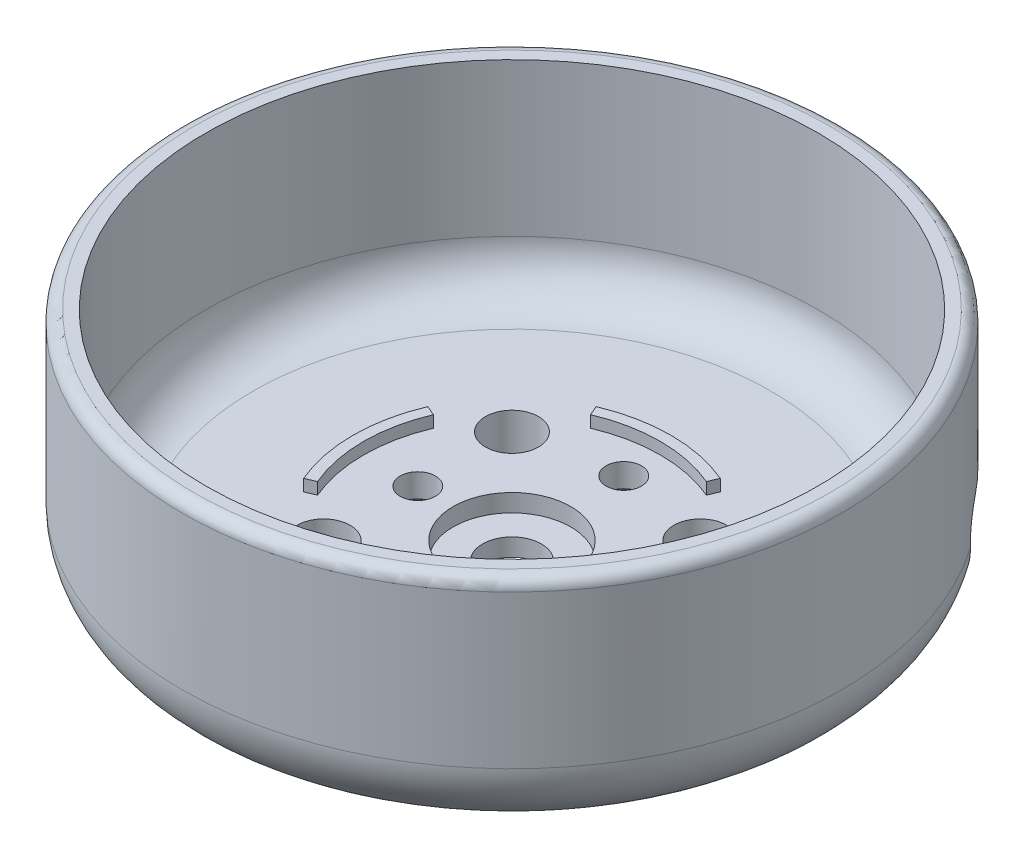
SolidWorks part; units mm, degrees
ref_plane "Front Plane" through (0, 0, 0) normal (0, 0, 1) x (1, 0, 0)
ref_plane "Top Plane" through (0, 0, 0) normal (0, 1, 0) x (1, 0, 0)
ref_plane "Right Plane" through (0, 0, 0) normal (1, 0, 0) x (0, 0, -1)
sketch "Sketch1" plane through (0, 0, 0) normal (0, 1, 0) x (1, 0, 0)
  circle A0 centre (0, 0) radius 9.5 construction
  circle A1 centre (0, 0) radius 8 construction
  circle A2 centre (0, 9.5) radius 1.5
  circle A3 centre (0, -9.5) radius 1.5
  circle A4 centre (-8, 0) radius 1.5
  circle A5 centre (8, 0) radius 1.5
  circle A6 centre (0, 0) radius 2.5
  circle A7 centre (0, 0) radius 26
  dimension "D1" = 8
  dimension "D3" = 3
  dimension "D4" = 3
  dimension "D5" = 3
  dimension "D6" = 3
  dimension "D7" = 52
  dimension "D8" = 5
  dimension "D2" = 9.5
extrude "Boss-Extrude1" add sketch "Sketch1" along normal blind 3
chamfer "Chamfer2" distance 1 angle 45 4 edges at (-8, 0, 1.5) (0, 0, -8) (8, 0, 1.5) (0, 0, 11)
sketch "Sketch3" plane through (0, 0, 0) normal (0, -1, 0) x (1, 0, 0)
  circle A0 centre (0, 0) radius 26 construction
  circle A1 centre (0, 0) radius 26
  circle A2 centre (0, 0) radius 28
  dimension "D1" = 2
extrude "Boss-Extrude3" add sketch "Sketch3" against normal blind 20
fillet "Fillet3" radius 4 1 edges at (0, 3, 26)
fillet "Fillet4" radius 6 1 edges at (0, 0, -28)
sketch "Sketch4" plane through (0, 3, 0) normal (0, 1, 0) x (1, 0, 0)
  line L0 (-9.5459, 9.5459) -> (9.5459, -9.5459) construction
  line L1 (-9.5459, -9.5459) -> (9.5459, 9.5459) construction
  line L2 (0, 0) -> (0, 22) construction
  line L3 (0, 0) -> (-5.2749, 12.4268) construction
  line L4 (0, 0) -> (-12.4268, 5.2749) construction
  line L5 (-12.4268, 5.2749) -> (-11.5984, 4.9232)
  line L6 (-5.2749, 12.4268) -> (-4.9232, 11.5984)
  line L7 (12.4268, 5.2749) -> (11.5984, 4.9232)
  line L8 (5.2749, 12.4268) -> (4.9232, 11.5984)
  line L9 (5.2749, -12.4268) -> (4.9232, -11.5984)
  line L10 (12.4268, -5.2749) -> (11.5984, -4.9232)
  line L11 (-12.4268, -5.2749) -> (-11.5984, -4.9232)
  line L12 (-5.2749, -12.4268) -> (-4.9232, -11.5984)
  arc A0 (-11.5984, 4.9232) -> (-11.5984, -4.9232) centre (0, 0) ccw
  arc A1 (-12.4268, 5.2749) -> (-12.4268, -5.2749) centre (0, 0) ccw
  circle A2 centre (0, 0) radius 22 construction
  arc A3 (-4.9232, -11.5984) -> (4.9232, -11.5984) centre (0, 0) ccw
  arc A4 (-5.2749, -12.4268) -> (5.2749, -12.4268) centre (0, 0) ccw
  arc A5 (11.5984, -4.9232) -> (11.5984, 4.9232) centre (0, 0) ccw
  arc A6 (12.4268, -5.2749) -> (12.4268, 5.2749) centre (0, 0) ccw
  arc A7 (4.9232, 11.5984) -> (-4.9232, 11.5984) centre (0, 0) ccw
  arc A8 (5.2749, 12.4268) -> (-5.2749, 12.4268) centre (0, 0) ccw
  point P21 (0, 0)
  point P30 (0, 0)
  dimension "D1" = 25.2
  dimension "D2" = 27
  dimension "D3" = 45
  dimension "D4" = 45
  dimension "D5" = 22
  dimension "D6" = 22
  dimension "D7" = 4
extrude "Boss-Extrude4" add sketch "Sketch4" along normal blind 1
sketch "Sketch5" plane through (0, 0, 0) normal (0, -1, 0) x (1, 0, 0)
  line L1 (-8, -8) -> (8, -8) construction
  line L2 (-8, -8) -> (-8, 8) construction
  line L3 (-8, 8) -> (8, 8) construction
  line L4 (8, -8) -> (8, 8) construction
  line L5 (-8, -8) -> (8, 8) construction
  line L6 (-8, 8) -> (8, -8) construction
  circle A1 centre (-8, 8) radius 2.25
  circle A2 centre (8, 8) radius 2.25
  circle A3 centre (8, -8) radius 2.25
  circle A4 centre (-8, -8) radius 2.25
  circle A5 centre (-8, 8) radius 4
  circle A6 centre (8, 8) radius 4
  circle A7 centre (8, -8) radius 4
  circle A8 centre (-8, -8) radius 4
  point P0 (0, 0)
  dimension "D1" = 16
  dimension "D3" = 4.5
  dimension "D4" = 4.5
  dimension "D5" = 4.5
  dimension "D6" = 4.5
  dimension "D7" = 8
  dimension "D8" = 8
  dimension "D9" = 8
  dimension "D10" = 8
  dimension "D2" = 16
extrude "Boss-Extrude5" add sketch "Sketch5" along normal blind 2.8
sketch "Sketch7" plane through (0, 0, 0) normal (0, -1, 0) x (1, 0, 0)
  circle A0 centre (-8, -8) radius 2.25 construction
  circle A1 centre (8, -8) radius 2.25 construction
  circle A2 centre (8, 8) radius 2.25 construction
  circle A3 centre (-8, 8) radius 2.25 construction
  circle A4 centre (-8, -8) radius 2.25
  circle A5 centre (8, -8) radius 2.25
  circle A6 centre (8, 8) radius 2.25
  circle A7 centre (-8, 8) radius 2.25
extrude "Cut-Extrude1" cut sketch "Sketch7" against normal blind 7
sketch "Sketch8" plane through (0, 3, 0) normal (0, 1, 0) x (1, 0, 0)
  circle A0 centre (0, 0) radius 5
  dimension "D1" = 10
extrude "Cut-Extrude2" cut sketch "Sketch8" against normal blind 1.5
fillet "Fillet5" radius 1 1 edges at (0, 20, -28)
ref_plane "Plane1" through (0, 0, 0) normal (-0.7071, 0, 0.7071) x (0.7071, 0, 0.7071)
sketch "Sketch9" plane through (0, 0, 0) normal (-0.7071, 0, 0.7071) x (0.7071, 0, 0.7071)
  line L1 (5, 3.5) -> (-5, 3.5)
  line L2 (5, 3.5) -> (5, 8.5)
  line L3 (5, 8.5) -> (-5, 8.5)
  line L4 (-5, 3.5) -> (-5, 8.5)
  line L5 (5, 3.5) -> (-5, 8.5) construction
  line L6 (5, 8.5) -> (-5, 3.5) construction
  point P0 (0, 6)
  dimension "D1" = 10
  dimension "D2" = 5
  dimension "D3" = 6
extrude "Cut-Extrude3" cut sketch "Sketch9" against normal blind 20 from offset 20 offset against normal yes
fillet "Fillet6" radius 2 4 edges at (22.2967, 8.5, -15.2257) (15.2257, 8.5, -22.2967) (14.2849, 3.5, -21.3559) (21.3559, 3.5, -14.2849)
